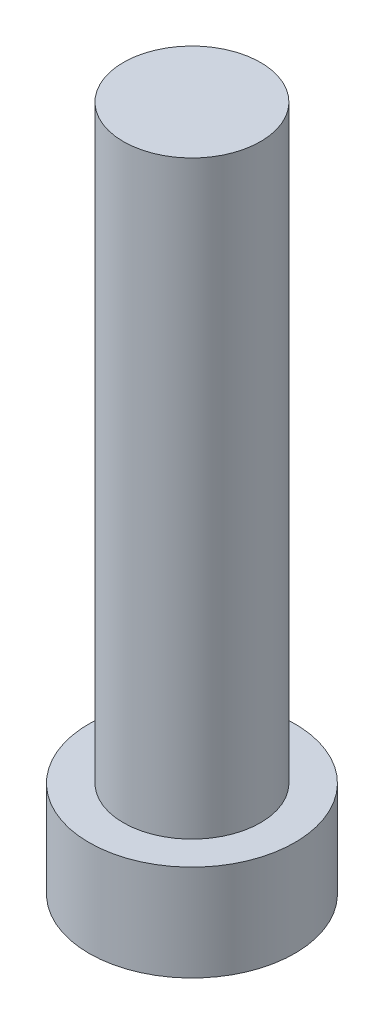
SolidWorks part; units mm, degrees
ref_plane "Front Plane" through (0, 0, 0) normal (0, 0, 1) x (1, 0, 0)
ref_plane "Top Plane" through (0, 0, 0) normal (0, 1, 0) x (1, 0, 0)
ref_plane "Right Plane" through (0, 0, 0) normal (1, 0, 0) x (0, 0, -1)
sketch "Sketch1" plane through (0, 0, 0) normal (0, 1, 0) x (1, 0, 0)
  line L0 (0, 0) -> (0, 8981.751) construction
  line L1 (0, 0) -> (8981.751, 0) construction
  circle A0 centre (0, 0) radius 7.5
  circle A1 centre (0, 0) radius 5
  dimension "D1" = 15
  dimension "D2" = 10
extrude "Boss-Extrude1" add sketch "Sketch1" along normal blind 7
extrude "Boss-Extrude2" add sketch "Sketch1<2>" along normal blind 50 contours A1 region at (0, 0, 0)
sketch "Sketch1<2>" plane through (0, 0, 0) normal (0, 1, 0) x (1, 0, 0) same geometry as "Sketch1"
